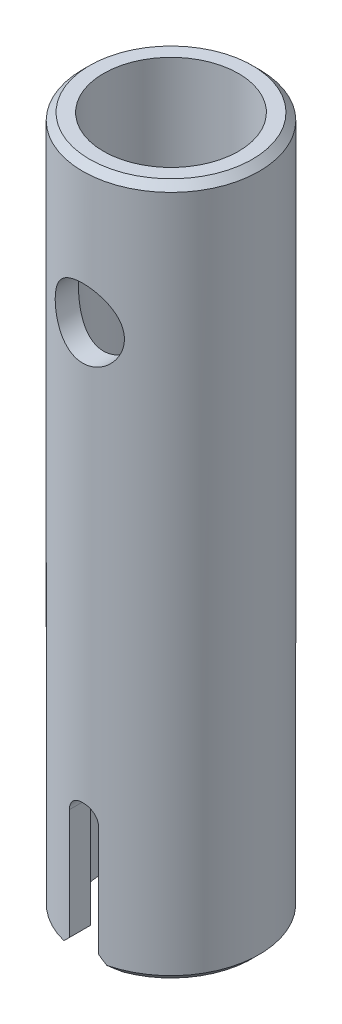
SolidWorks part; units mm, degrees
material "Stainless Steel (ferritic)"
ref_plane "Front Plane" through (0, 0, 0) normal (0, 0, 1) x (1, 0, 0)
ref_plane "Top Plane" through (0, 0, 0) normal (0, 1, 0) x (1, 0, 0)
ref_plane "Right Plane" through (0, 0, 0) normal (1, 0, 0) x (0, 0, -1)
sketch "Sketch1" plane through (0, 0, 0) normal (0, 1, 0) x (1, 0, 0)
  circle A0 centre (0, 0) radius 4.875
  circle A1 centre (0, 0) radius 6.375
  dimension "D1" = 9.75
  dimension "D2" = 1.5
extrude "Boss-Extrude1" add sketch "Sketch1" along normal blind 50
ref_plane "Plane1" through (0, 0, -6.375) normal (0, 0, -1) x (-1, 0, 0)
ref_axis "Axis1" through (0, -2.5, -6.375) along (0, 1, 0)
ref_axis "Axis2" through (7.0125, 0, -6.375) along (-1, 0, 0)
sketch "Sketch2" plane through (0, 0, -6.375) normal (0, 0, -1) x (-1, 0, 0)
  line L0 (0, -2.5) -> (0, 52.5) construction
  line L1 (1.05, 0) -> (-1.05, 0)
  line L2 (1.05, 0) -> (1.05, 10)
  line L3 (1.05, 10) -> (-1.05, 10)
  line L4 (-1.05, 0) -> (-1.05, 10)
  line L5 (-7.0125, 0) -> (7.0125, 0) construction
  point P4 (0, 0)
  dimension "D1" = 10
  dimension "D2" = 2.1
extrude "Cut-Extrude1" cut sketch "Sketch2" against normal through all
sketch "Sketch3" plane through (0, 0, -6.375) normal (0, 0, -1) x (-1, 0, 0)
  line L0 (2.05, 0) -> (-2.05, 0)
  line L1 (-7.0125, 0) -> (7.0125, 0) construction
  line L2 (0, -2.5) -> (0, 52.5) construction
  line L3 (2.05, 0) -> (0, 2.05)
  line L4 (0, 2.05) -> (-2.05, 0)
  point P2 (0, 0)
  dimension "D1" = 45
  dimension "D2" = 4.1
extrude "Cut-Extrude2" cut sketch "Sketch3" against normal through all
fillet "Fillet1" radius 1 4 edges at (1.05, 10, 5.5243) (-1.05, 10, 5.5243) (1.05, 10, -5.5243) (-1.05, 10, -5.5243)
chamfer "Chamfer1" distance 0.5 angle 45 3 edges at (6.375, 0, 0) (-6.375, 0, 0) (0, 50, 6.375)
sketch "Sketch4" plane through (0, 0, -6.375) normal (0, 0, -1) x (-1, 0, 0)
  line L0 (0, -2.5) -> (0, 52.5) construction
  line L1 (-7.0125, 0) -> (7.0125, 0) construction
  circle A0 centre (0, 40) radius 2.5
  dimension "D2" = 5
  dimension "D1" = 40
extrude "Cut-Extrude3" cut sketch "Sketch4" against normal through all
